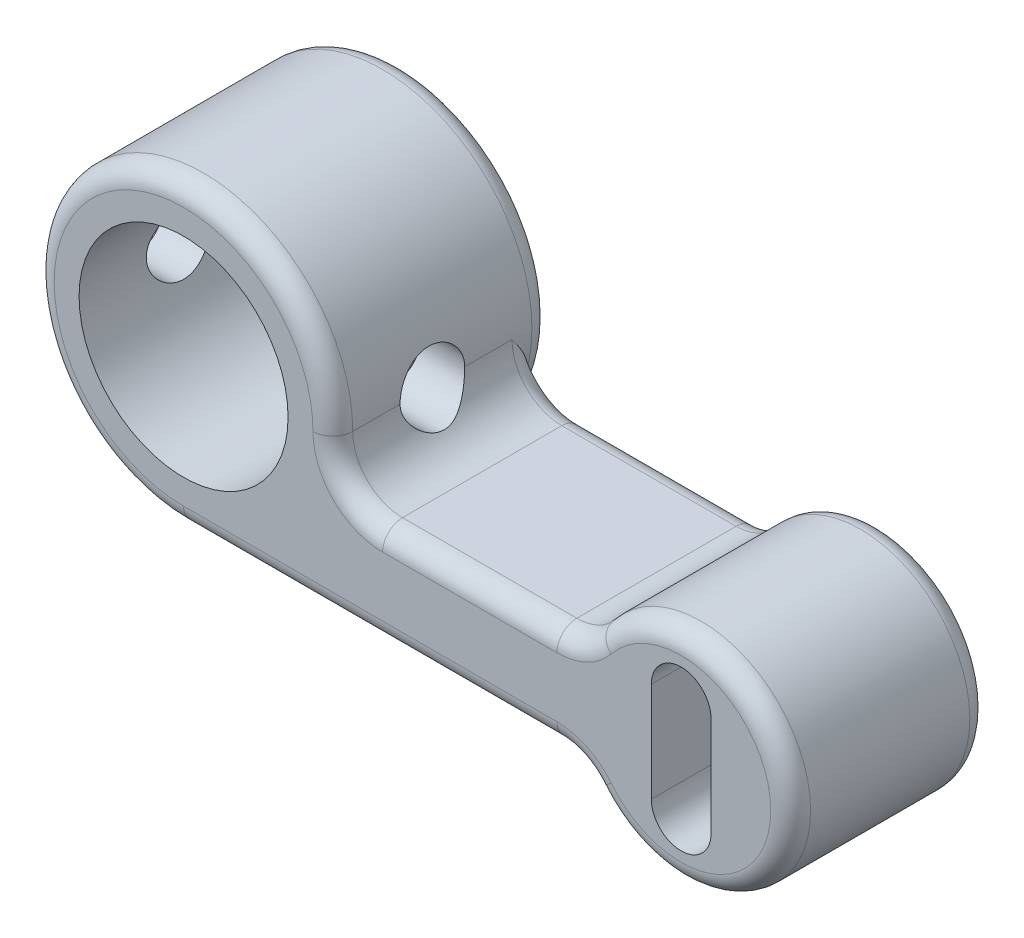
SolidWorks part; units mm, degrees
ref_plane "前视基准面" through (0, 0, 0) normal (0, 0, 1) x (1, 0, 0)
ref_plane "上视基准面" through (0, 0, 0) normal (0, 1, 0) x (1, 0, 0)
ref_plane "右视基准面" through (0, 0, 0) normal (1, 0, 0) x (0, 0, -1)
sketch "草图1" plane through (0, 0, 0) normal (0, 0, 1) x (1, 0, 0)
  circle A0 centre (0, 0) radius 10.5
  circle A1 centre (0, 0) radius 15
extrude "凸台-拉伸1" add sketch "草图1" along normal mid plane 20
sketch "草图2" plane through (0, 0, 0) normal (1, 0, 0) x (0, 0, -1)
  circle A0 centre (0, 0) radius 3.25
extrude "切除-拉伸1" cut sketch "草图2" against normal through all both and the other way through all
sketch "草图3" plane through (0, 0, 0) normal (0, 0, 1) x (1, 0, 0)
  line L0 (0, 0) -> (0, -15) construction
  line L1 (0, -15) -> (50, -15) construction
  line L2 (50, -15) -> (50, -10) construction
  line L3 (50, -10) -> (50, -5) construction
  line L4 (50, -10) -> (11.1803, -10) construction
  line L5 (50, -5) -> (14.1421, -5) construction
  line L6 (0, -15) -> (0, -20) construction
  line L7 (0, -20) -> (50, -20) construction
  line L8 (50, -20) -> (50, -15) construction
  line L9 (50, -15) -> (50, -5) construction
  line L10 (47, -15) -> (47, -5)
  line L11 (53, -15) -> (53, -5)
  circle A0 centre (0, 0) radius 15 construction
  circle A1 centre (50, -10) radius 5 construction
  arc A2 (47, -15) -> (53, -15) centre (50, -15) ccw
  arc A3 (53, -5) -> (47, -5) centre (50, -5) ccw
  circle A6 centre (50, -10) radius 11
  point P14 (50, -10)
extrude "凸台-拉伸2" add sketch "草图3" along normal mid plane 20 separate body
sketch "草图4" plane through (0, 0, 0) normal (0, 0, 1) x (1, 0, 0)
  line L0 (0, 0) -> (0, -10) construction
  line L2 (40.202, -15) -> (0, -15)
  line L4 (40.202, -5) -> (14.1421, -5)
  arc A0 (0, -15) -> (14.1421, -5) centre (0, 0) ccw
  circle A2 centre (0, 0) radius 15 construction
  arc A3 (40.202, -5) -> (40.202, -15) centre (50, -10) ccw
extrude "凸台-拉伸3" add sketch "草图4" along normal mid plane 20
fillet "圆角1" radius 5 3 edges at (14.1421, -5, 0) (40.202, -15, 0) (40.202, -5, 0)
sketch "草图5" plane through (0, 0, -10) normal (0, 0, -1) x (-1, 0, 0)
  circle A0 centre (0, 0) radius 10.5 construction
  circle A1 centre (0, 0) radius 15
extrude "凸台-拉伸4" add sketch "草图5" along normal blind 2
fillet "圆角3" radius 2 7 edges at (18.755, -15, -10) (39.6751, -15.4931, -10) (61, -10, -10) (39.6751, -4.5069, -10) (16.4645, -3.5355, -10) (28.755, -5, -10) (-15, 0, -12)
fillet "圆角4" radius 2 7 edges at (16.4645, -3.5355, 10) (28.755, -5, 10) (39.6751, -4.5069, 10) (61, -10, 10) (39.6751, -15.4931, 10) (18.755, -15, 10) (-10.6066, 10.6066, 10)
